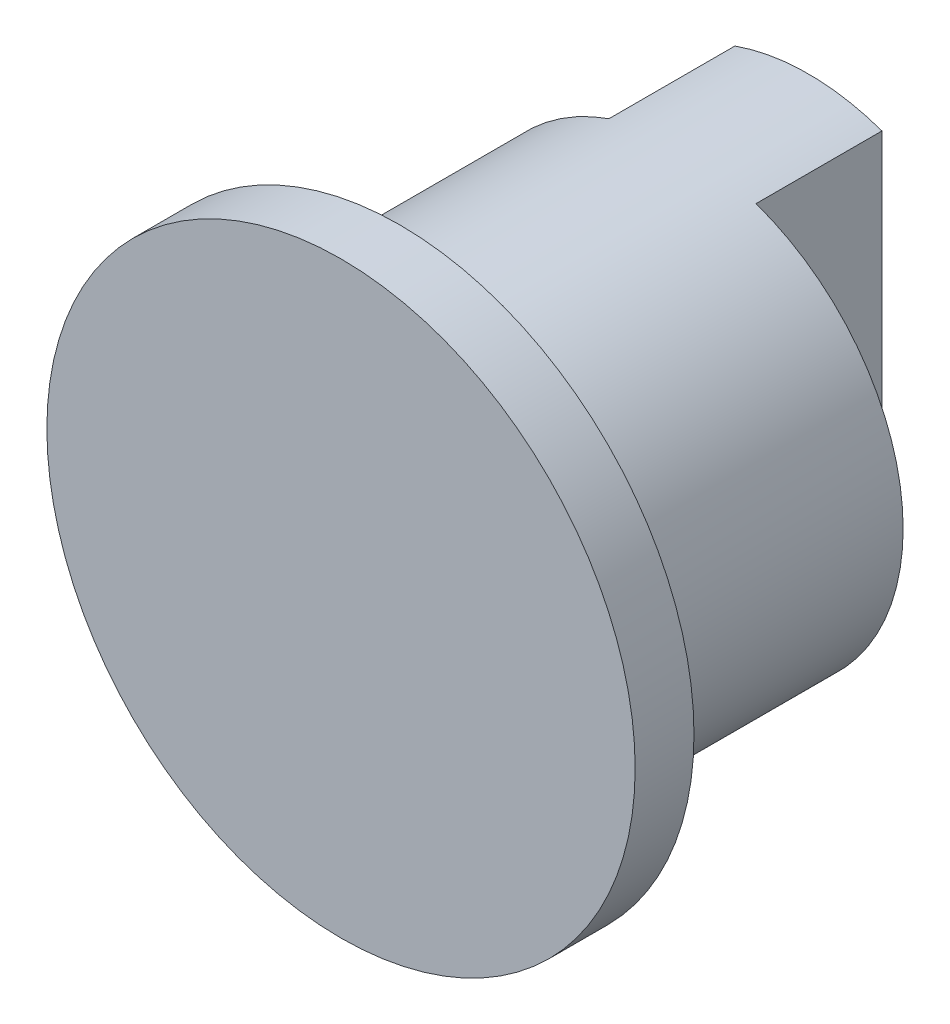
SolidWorks part; units mm, degrees
material "1060 Alloy"
ref_plane "Front Plane" through (0, 0, 0) normal (0, 0, 1) x (1, 0, 0)
ref_plane "Top Plane" through (0, 0, 0) normal (0, 1, 0) x (1, 0, 0)
ref_plane "Right Plane" through (0, 0, 0) normal (1, 0, 0) x (0, 0, -1)
sketch "Sketch1" plane through (0, 0, 0) normal (0, 0, 1) x (1, 0, 0)
  circle A0 centre (0, 0) radius 4.7625
  dimension "D1" = 9.525
extrude "Boss-Extrude1" add sketch "Sketch1" along normal blind 10.0901
sketch "Sketch2" plane through (0, 0, 0) normal (0, 1, 0) x (1, 0, 0)
  line L0 (4.7625, 0) -> (-4.7625, 0) construction
  line L1 (-4.7625, 0.4572) -> (-1.5875, 0.4572)
  line L2 (-4.7625, 0.4572) -> (-4.7625, -2.7178)
  line L3 (-4.7625, -2.7178) -> (-1.5875, -2.7178)
  line L4 (-1.5875, 0.4572) -> (-1.5875, -2.7178)
  line L5 (6.2298, 0.4747) -> (5.8946, 0.4747)
  line L6 (6.2298, 0.4747) -> (6.2298, 0.335)
  line L7 (6.2298, 0.335) -> (5.8946, 0.335)
  line L8 (5.8946, 0.4747) -> (5.8946, 0.335)
  line L9 (4.7625, 0.4572) -> (1.5875, 0.4572)
  line L10 (4.7625, 0.4572) -> (4.7625, -2.7178)
  line L11 (4.7625, -2.7178) -> (1.5875, -2.7178)
  line L12 (1.5875, 0.4572) -> (1.5875, -2.7178)
  dimension "D1" = 9.525
  dimension "D2" = 4.7625
  dimension "D3" = 3.175
  dimension "D4" = 3.175
  dimension "D5" = 3.175
  dimension "D6" = 3.175
  dimension "D7" = 2.7178
  dimension "D8" = 2.7178
extrude "Cut-Extrude1" cut sketch "Sketch2" against normal blind 13.4937 and the other way blind 13.4937
hole_wizard "#4-40 Tapped Hole1" positions "Sketch5" profile "Sketch4" tap size "#4-40" standard "Ansi Inch"
sketch "Sketch5" plane through (0, 0, 0) normal (0, 0, -1) x (-1, 0, 0)
  line L0 (-1.5875, -4.4901) -> (-1.5875, 4.4901) construction
  arc A0 (1.5875, 4.4901) -> (-1.5875, 4.4901) centre (0, 0) ccw construction
  point P0 (0, 0)
  dimension "D1" = 1.5875
  dimension "D2" = 0
sketch "Sketch4" plane through (0, 0, 0) normal (1, 0, 0) x (0, 1, 0)
  line L0 (0, 0) -> (0, 9.5438)
  line L1 (0, 9.5438) -> (1.1303, 8.8646)
  line L2 (1.1303, 8.8646) -> (1.1303, 0)
  line L5 (1.1303, 0) -> (0, 0)
  line L10 (0, 9.5438) -> (-1.1303, 8.8646) construction
  line L11 (0, -6.35) -> (0, 107.95) construction
  dimension "Tap Drill Dia." = 2.2606
  dimension "Tap Drill Depth" = 8.8646
  dimension "Drill Angle" = 118
sketch "Sketch6" plane through (0, 0, 10.0901) normal (0, 0, 1) x (1, 0, 0)
  circle A0 centre (0, 0) radius 6.35
  dimension "D1" = 12.7
extrude "Boss-Extrude2" add sketch "Sketch6" against normal blind 1.27
